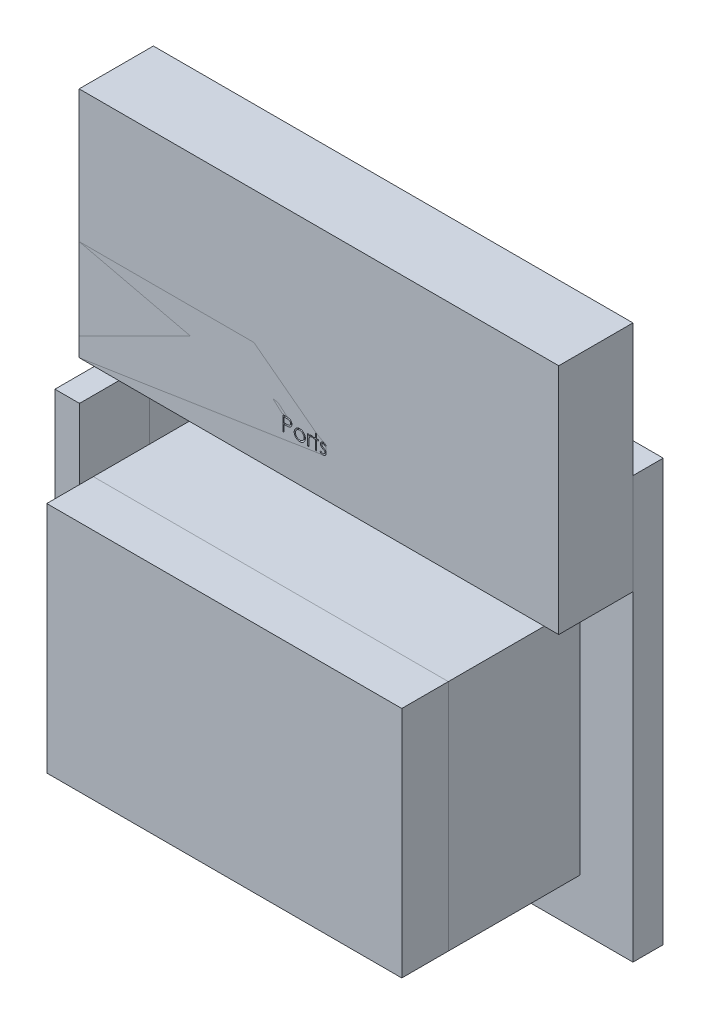
SolidWorks part; units mm, degrees
ref_plane "Front Plane" through (0, 0, 0) normal (0, 0, 1) x (1, 0, 0)
ref_plane "Top Plane" through (0, 0, 0) normal (0, 1, 0) x (1, 0, 0)
ref_plane "Right Plane" through (0, 0, 0) normal (1, 0, 0) x (0, 0, -1)
sketch "Sketch1" plane through (0, 0, 0) normal (0, 0, 1) x (1, 0, 0)
  line L1 (0, 0) -> (103, 0)
  line L2 (0, 0) -> (0, 90.5)
  line L3 (0, 90.5) -> (103, 90.5)
  line L4 (103, 0) -> (103, 90.5)
  dimension "D1" = 90.5
  dimension "D2" = 103
extrude "Boss-Extrude1" add sketch "Sketch1" against normal blind 6.5
sketch "Sketch2" plane through (0, 0, 0) normal (0, 0, 1) x (1, 0, 0)
  line L0 (0, 90.5) -> (0, 0) construction
  line L1 (15.38, 60.63) -> (91.62, 60.63)
  line L2 (15.38, 60.63) -> (15.38, 10.5)
  line L3 (15.38, 10.5) -> (91.62, 10.5)
  line L4 (91.62, 60.63) -> (91.62, 10.5)
  line L5 (0, 0) -> (103, 0) construction
  line L6 (103, 0) -> (103, 90.5) construction
  line L7 (8.14, 68.5) -> (2.86, 68.5)
  line L8 (8.14, 68.5) -> (8.14, 17.5)
  line L9 (8.14, 17.5) -> (2.86, 17.5)
  line L10 (2.86, 68.5) -> (2.86, 17.5)
  line L11 (0, 90.5) -> (103, 90.5)
  line L12 (0, 90.5) -> (0, 68.9)
  line L13 (0, 68.9) -> (103, 68.9)
  line L14 (103, 90.5) -> (103, 68.9)
  dimension "D1" = 76.24
  dimension "D2" = 50.13
  dimension "D3" = 15.38
  dimension "D4" = 10.5
  dimension "D5" = 5.28
  dimension "D6" = 51
  dimension "D7" = 17.5
  dimension "D8" = 2.86
  dimension "D9" = 21.6
extrude "Boss-Extrude2" add sketch "Sketch2" along normal blind 28.27 contours L2 L1 L4 L3
extrude "Boss-Extrude3" add sketch "Sketch2<4>" along normal blind 9 contours L8 L9 L10 L7
sketch "Sketch2<4>" plane through (0, 0, 0) normal (0, 0, 1) x (1, 0, 0) same geometry as "Sketch2"
extrude "Boss-Extrude4" add sketch "Sketch2<5>" along normal blind 15.94 contours L13 L14 L11 L12
sketch "Sketch2<5>" plane through (0, 0, 0) normal (0, 0, 1) x (1, 0, 0) same geometry as "Sketch2"
sketch "Sketch6" plane through (0, 0, 15.94) normal (0, 0, 1) x (1, 0, 0)
  text T0 "Ports"
sketch "Sketch7" plane through (0, 0, 9) normal (0, 0, 1) x (1, 0, 0)
  line L0 (4.2988, 68.5) -> (4.2988, 17.5) construction
  line L1 (8.14, 68.5) -> (2.86, 68.5) construction
  line L2 (8.14, 17.5) -> (2.86, 17.5) construction
  text T0 "Pins"
sketch "Sketch8" plane through (0, 0, 28.27) normal (0, 0, 1) x (1, 0, 0)
  text T0 "Chip"
sketch "Sketch9" plane through (0, 0, 28.27) normal (0, 0, 1) x (1, 0, 0)
  line L1 (15.38, 60.63) -> (91.62, 60.63)
  line L2 (15.38, 60.63) -> (15.38, 10.5)
  line L3 (15.38, 10.5) -> (91.62, 10.5)
  line L4 (91.62, 60.63) -> (91.62, 10.5)
extrude "Boss-Extrude5" add sketch "Sketch9" along normal blind 10 separate body
sketch "Sketch10" plane through (0, 68.9, 0) normal (0, -1, 0) x (1, 0, 0)
  line L1 (0, 15.94) -> (103, 15.94)
  line L2 (0, 15.94) -> (0, 0)
  line L3 (0, 0) -> (103, 0)
  line L4 (103, 15.94) -> (103, 0)
extrude "Boss-Extrude6" add sketch "Sketch10" against normal blind 50 separate body
extrude "Cut-Extrude1" cut sketch "Sketch6" against normal blind 1
extrude "Cut-Extrude2" cut sketch "Sketch8" against normal blind 1
extrude "Cut-Extrude3" cut sketch "Sketch7" against normal blind 1
sketch "Sketch11" plane through (0, 0, 9) normal (0, 0, 1) x (1, 0, 0)
  line L1 (2.86, 68.5) -> (8.14, 68.5)
  line L2 (2.86, 68.5) -> (2.86, 17.5)
  line L3 (2.86, 17.5) -> (8.14, 17.5)
  line L4 (8.14, 68.5) -> (8.14, 17.5)
extrude "Boss-Extrude7" add sketch "Sketch11" along normal blind 15 separate body
